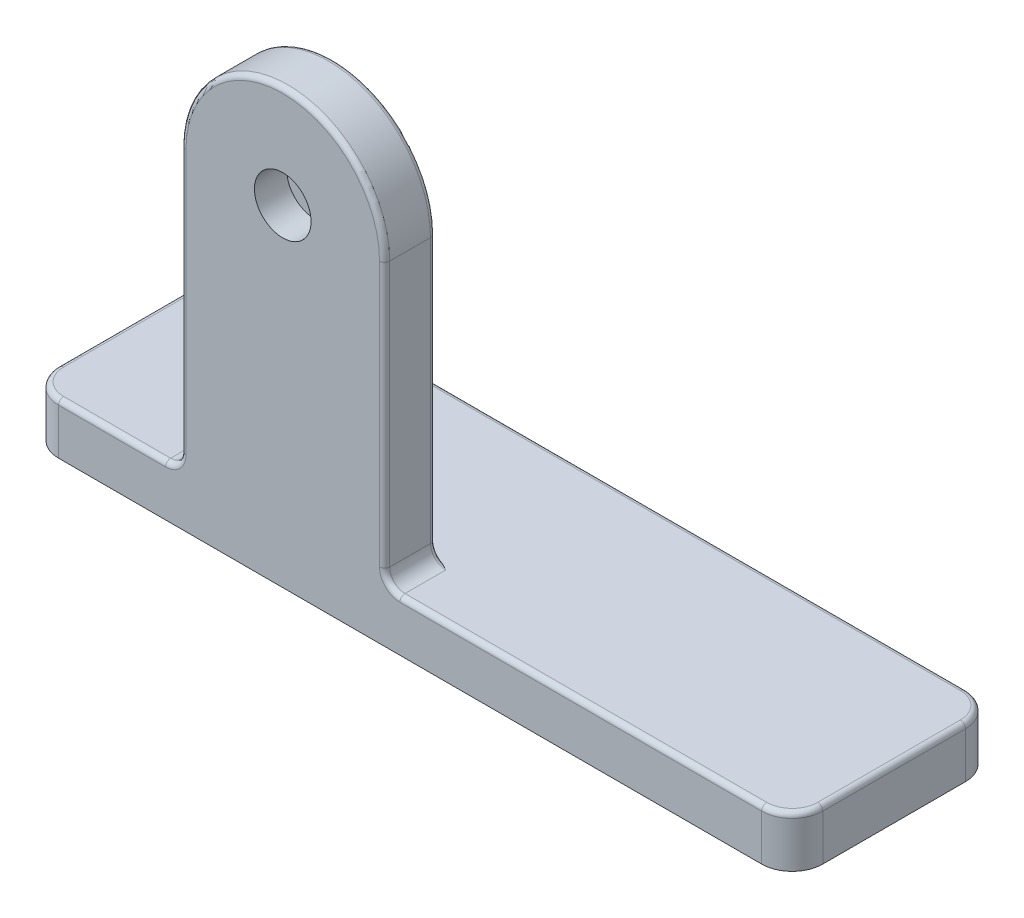
SolidWorks part; units mm, degrees
ref_plane "Front Plane" through (0, 0, 0) normal (0, 0, 1) x (1, 0, 0)
ref_plane "Top Plane" through (0, 0, 0) normal (0, 1, 0) x (1, 0, 0)
ref_plane "Right Plane" through (0, 0, 0) normal (1, 0, 0) x (0, 0, -1)
sketch "Sketch1" plane through (0, 0, 0) normal (0, 1, 0) x (1, 0, 0)
  line L1 (75, -20) -> (-75, -20)
  line L2 (75, -20) -> (75, 20)
  line L3 (75, 20) -> (-75, 20)
  line L4 (-75, -20) -> (-75, 20)
  line L5 (0, 20) -> (0, -20) construction
  line L6 (75, 0) -> (-75, 0) construction
  point P0 (0, 0)
  dimension "D1" = 150
  dimension "D2" = 40
extrude "Boss-Extrude1" add sketch "Sketch1" along normal blind 10
sketch "Sketch2" plane through (0, 0, 20) normal (0, 0, 1) x (1, 0, 0)
  line L0 (-75, 0) -> (75, 0) construction
  line L1 (-45, 0) -> (-5, 0)
  line L2 (-45, 0) -> (-45, 65)
  line L3 (-45, 65) -> (-5, 65) construction
  line L4 (-5, 0) -> (-5, 65)
  line L5 (-75, 10) -> (-75, 0) construction
  arc A0 (-5, 65) -> (-45, 65) centre (-25, 65) ccw
  dimension "D1" = 20
  dimension "D2" = 65
  dimension "D3" = 50
extrude "Boss-Extrude2" add sketch "Sketch2" against normal blind 10
hole_wizard "CBORE for 1/4 Socket Head Cap Screw1" positions "Sketch9" profile "Sketch5" counterbore size "1/4" standard "ANSI Inch" end condition up to next
sketch "Sketch9" plane through (0, 0, 20) normal (0, 0, 1) x (1, 0, 0)
  point P0 (-25, 65)
sketch "Sketch5" plane through (-25, 65, 20) normal (1, 0, 0) x (0, -1, 0)
  line L0 (0, 0) -> (0, 10)
  line L1 (0, 10) -> (3.3782, 10)
  line L3 (3.3782, 10) -> (3.3782, 6.35)
  line L4 (3.3782, 6.35) -> (5.5562, 6.35)
  line L5 (5.5562, 6.35) -> (5.5562, 0)
  line L7 (5.5562, 0) -> (0, 0)
  line L11 (0, -6.35) -> (0, 107.95) construction
  dimension "Thru Hole Dia." = 6.7564
  dimension "Thru Hole Depth" = 10
  dimension "C'Bore Dia." = 11.1125
  dimension "C'Bore Depth" = 6.35
fillet "Fillet1" radius 6 4 edges at (75, 5, -20) (-75, 5, -20) (-75, 5, 20) (75, 5, 20)
fillet "Fillet2" radius 3 2 edges at (-45, 10, 15) (-5, 10, 15)
fillet "Fillet3" radius 1 19 edges at (-4.1213, 10.8787, 10) (-5, 39, 10) (-45.8787, 10.8787, 10) (-45, 39, 10) (73.2426, 10, -18.2426) (75, 10, 0) (73.2426, 10, 18.2426) (33.5, 10, 20) (-4.1213, 10.8787, 20) (-5, 39, 20) (-25, 85, 20) (-58.5, 10, 20) (-73.2426, 10, 18.2426) (-75, 10, 0) (-73.2426, 10, -18.2426) (-45.8787, 10.8787, 20) (-45, 39, 20) (-25, 85, 10) (0, 10, -20)
shell "Shell4" thickness 2 removed face at (0, 0, 0)
